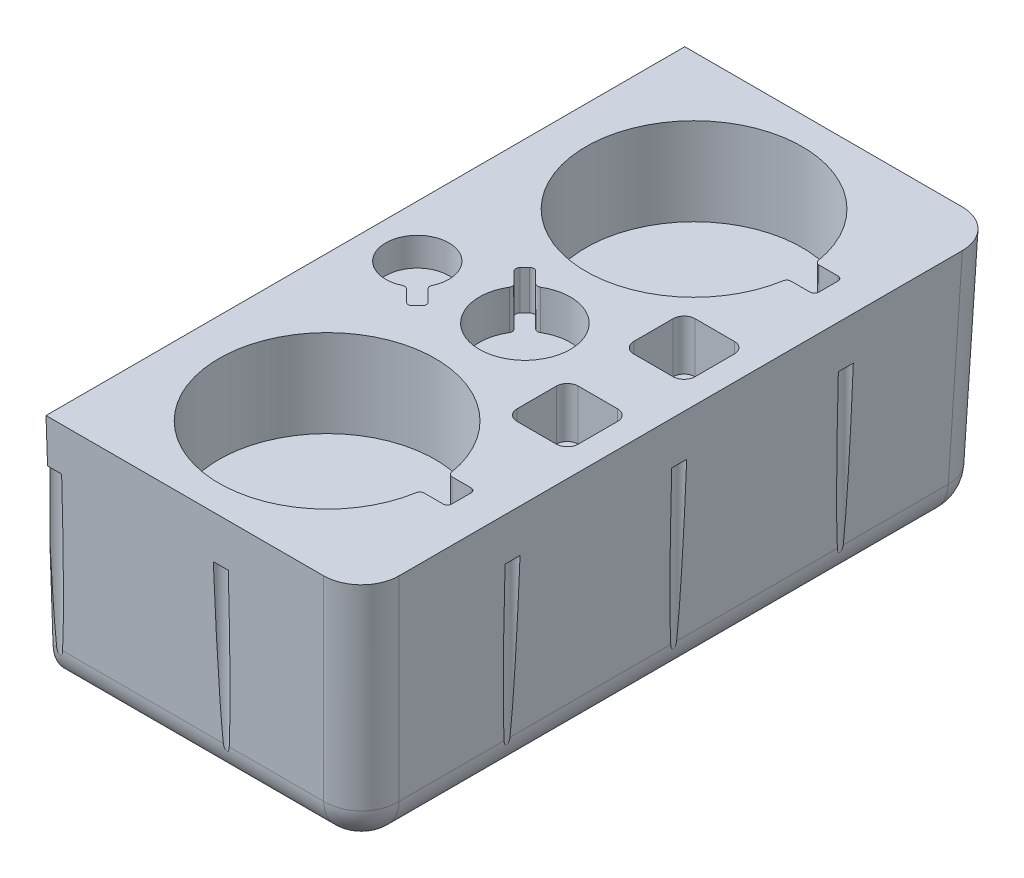
SolidWorks part; units mm, degrees
ref_plane "Front Plane" through (0, 0, 0) normal (0, 0, 1) x (1, 0, 0)
ref_plane "Top Plane" through (0, 0, 0) normal (0, 1, 0) x (1, 0, 0)
ref_plane "Right Plane" through (0, 0, 0) normal (1, 0, 0) x (0, 0, -1)
sketch "Sketch3" plane through (0, 0, 0) normal (0, 1, 0) x (1, 0, 0)
  line L1 (-70.2, -142.24) -> (70.2, -142.24)
  line L2 (-70.2, -142.24) -> (-70.2, 142.24)
  line L3 (-70.2, 142.24) -> (70.2, 142.24)
  line L4 (70.2, -142.24) -> (70.2, 142.24)
  line L5 (-70.2, -142.24) -> (70.2, 142.24) construction
  line L6 (-70.2, 142.24) -> (70.2, -142.24) construction
  point P0 (0, 0)
  dimension "D1" = 140.4
  dimension "D2" = 284.48
extrude "Boss-Extrude1" add sketch "Sketch3" along normal blind 109.22 draft 2 draft outward yes
sketch "Sketch1" plane through (0, 0, 0) normal (0, 1, 0) x (1, 0, 0)
  line L0 (45.236, 90.304) -> (57.636, 90.304)
  line L5 (57.636, 90.304) -> (57.636, 77.504)
  line L6 (57.636, 77.504) -> (45.236, 77.504)
  line L7 (45.236, -77.504) -> (57.636, -77.504)
  line L8 (57.636, -77.504) -> (57.636, -90.304)
  line L9 (57.636, -90.304) -> (45.236, -90.304)
  line L16 (39.838, 12.7) -> (57.838, 12.7)
  line L17 (34.838, 17.7) -> (34.838, 35.7)
  line L18 (39.838, 40.7) -> (57.838, 40.7)
  line L19 (62.838, 17.7) -> (62.838, 35.7)
  line L20 (34.838, 12.7) -> (62.838, 40.7) construction
  line L21 (34.838, 40.7) -> (62.838, 12.7) construction
  line L22 (39.838, -40.7) -> (57.838, -40.7)
  line L23 (34.838, -35.7) -> (34.838, -17.7)
  line L24 (39.838, -12.7) -> (57.838, -12.7)
  line L25 (62.838, -35.7) -> (62.838, -17.7)
  line L26 (34.838, -40.7) -> (62.838, -12.7) construction
  line L27 (34.838, -12.7) -> (62.838, -40.7) construction
  line L28 (-72.9829, 0) -> (78.453, 0) construction
  line L29 (74.014, 146.054) -> (-74.014, 146.054) construction
  line L31 (-74.014, 146.054) -> (-74.014, -146.054) construction
  line L34 (74.014, -146.054) -> (74.014, 146.054) construction
  line L35 (-74.014, -146.054) -> (74.014, -146.054) construction
  line L42 (-16.8542, 24.539) -> (-9.2882, 16.973)
  line L43 (-16.8542, 24.539) -> (-21.804, 19.5893)
  line L44 (-21.804, 19.5893) -> (-14.2379, 12.0232)
  line L45 (-19.3291, 22.0641) -> (2.735, 0) construction
  line L46 (-46.4604, 0) -> (-28.7687, -17.6916) construction
  line L47 (-39.0218, -12.3883) -> (-31.2436, -20.1665)
  line L48 (-31.2436, -20.1665) -> (-26.2939, -15.2167)
  line L49 (-26.2939, -15.2167) -> (-34.072, -7.4386)
  arc A0 (45.236, 90.304) -> (45.236, 77.504) centre (-3.798, 83.904) ccw
  arc A1 (45.236, -77.504) -> (45.236, -90.304) centre (-3.798, -83.904) ccw
  arc A4 (57.838, 40.7) -> (62.838, 35.7) centre (57.838, 35.7) cw
  arc A5 (57.838, 12.7) -> (62.838, 17.7) centre (57.838, 17.7) ccw
  arc A6 (39.838, 12.7) -> (34.838, 17.7) centre (39.838, 17.7) cw
  arc A7 (34.838, 35.7) -> (39.838, 40.7) centre (39.838, 35.7) cw
  arc A8 (39.838, -40.7) -> (34.838, -35.7) centre (39.838, -35.7) cw
  arc A9 (57.838, -40.7) -> (62.838, -35.7) centre (57.838, -35.7) ccw
  arc A10 (57.838, -12.7) -> (62.838, -17.7) centre (57.838, -17.7) cw
  arc A11 (34.838, -17.7) -> (39.838, -12.7) centre (39.838, -17.7) cw
  arc A12 (-34.072, -7.4386) -> (-39.0218, -12.3883) centre (-46.4604, 0) ccw
  arc A16 (-14.2379, 12.0232) -> (-9.2882, 16.973) centre (2.735, 0) ccw
  circle A17 centre (48.838, 26.7) radius 8.35
  circle A18 centre (48.838, -26.7) radius 8.35
  point P13 (48.838, 12.7)
  point P25 (48.838, 26.7)
  point P42 (48.838, -26.7)
  dimension "D3" = 98.9
  dimension "D4" = 98.9
  dimension "D8" = 20.8
  dimension "D11" = 11.303
  dimension "D15" = 5
  dimension "D18" = 5
  dimension "D5" = 12.7
  dimension "D19" = 77.8121
  dimension "D20" = 12.7
  dimension "D21" = 28.9
  dimension "D22" = 135
  dimension "D23" = 7
  dimension "D25" = 12.7
  dimension "D12" = 13.1037
  dimension "D13" = 45
  dimension "D27" = 16.7
  dimension "D1" = 12.4
  dimension "D2" = 12.8
  dimension "D6" = 12.8
  dimension "D7" = 12.4
  dimension "D9" = 7
  dimension "D10" = 10.7
  dimension "D14" = 28
  dimension "D16" = 28
  dimension "D17" = 28
  dimension "D24" = 11
  dimension "D26" = 11.176
fillet "Fillet1" radius 17.272 5 edges at (0, 0, -142.24) (0, 0, 142.24) (70.2, 0, 0) (72.107, 54.61, -144.147) (72.107, 54.61, 144.147)
extrude "Cut-Extrude1" cut sketch "Sketch1" against normal blind 40 from surface contours A0 L6 L5 L0 | A1 L9 L8 L7 starting at face at (20.1096, 109.22, 0)
extrude "Cut-Extrude2" cut sketch "Sketch1<4>" against normal blind 13 from surface contours L49 A12 L47 L48 region at (-45.034, 0, 1.4263) starting at face at (26.815, 109.22, 83.904)
sketch "Sketch1<4>" plane through (0, 0, 0) normal (0, 1, 0) x (1, 0, 0) same geometry as "Sketch1"
extrude "Cut-Extrude3" cut sketch "Sketch1<5>" against normal blind 18 from surface contours L44 A16 L42 L43 region at (1.7934, 0, -0.9416) starting at face at (-37.6906, 109.22, 8.7697)
sketch "Sketch1<5>" plane through (0, 0, 0) normal (0, 1, 0) x (1, 0, 0) same geometry as "Sketch1"
extrude "Cut-Extrude5" cut sketch "Sketch1<6>" against normal blind 23 from surface contours A7 L17 A6 L16 A5 L19 A4 L18 | A11 L23 A8 L22 A9 L25 A10 L24 region at (36.5825, 0, -14.4445) region at (36.5825, 0, 38.9555) starting at face at (-8.2446, 109.22, -10.9796)
sketch "Sketch1<6>" plane through (0, 0, 0) normal (0, 1, 0) x (1, 0, 0) same geometry as "Sketch1"
extrude "Cut-Extrude7" cut sketch "Sketch1<7>" against normal blind 31 from surface contours A17 | A18 region at (48.838, 0, -26.7) region at (48.838, 0, 26.7) starting at face at (48.838, 109.22, 26.7)
sketch "Sketch1<7>" plane through (0, 0, 0) normal (0, 1, 0) x (1, 0, 0) same geometry as "Sketch1"
fillet "Fillet2" radius 2 16 edges at (45.236, 89.22, 90.304) (45.236, 89.22, 77.504) (57.636, 89.22, 77.504) (57.636, 89.22, 90.304) (-31.2436, 102.72, 20.1665) (-26.2939, 102.72, 15.2167) (-34.072, 102.72, 7.4386) (-39.0218, 102.72, 12.3883) (-14.2379, 100.22, -12.0232) (-21.804, 100.22, -19.5893) (-16.8542, 100.22, -24.539) (-9.2882, 100.22, -16.973) (45.236, 89.22, -77.504) (57.636, 89.22, -90.304) (57.636, 89.22, -77.504) (45.236, 89.22, -90.304)
sketch "Sketch4" plane through (0, 0, 0) normal (0, 0, 1) x (1, 0, 0)
  line L1 (-74.014, 109.22) -> (56.7526, 109.22) construction
  line L2 (-70.2, 109.22) -> (-70.2, 0)
  line L3 (-70.2, 0) -> (-85.4637, 109.22)
  line L4 (-85.4637, 109.22) -> (-70.2, 109.22)
  dimension "D2" = 110.2814
extrude "Cut-Extrude8" cut sketch "Sketch4" against normal through all both and the other way through all contours L3 L4 L2
ref_plane "Plane1" through (0, 88.9, 0) normal (0, 1, 0) x (1, 0, 0)
sketch "Sketch6" plane through (0, 88.9, 0) normal (0, 1, 0) x (1, 0, 0)
  line L0 (74.014, -128.7926) -> (74.014, 128.7926) construction
  line L1 (74.014, 3.5) -> (74.014, -3.5)
  line L2 (74.014, 79.7) -> (74.014, 72.7)
  line L3 (-9.7237, 0) -> (10.798, 0) construction
  line L4 (74.014, -79.7) -> (74.014, -72.7)
  line L5 (56.7526, 146.054) -> (-70.2, 146.054) construction
  line L6 (5.514, 146.054) -> (12.514, 146.054)
  line L7 (-70.686, 146.054) -> (-63.686, 146.054)
  line L8 (-70.686, -146.054) -> (-63.686, -146.054)
  line L9 (5.514, -146.054) -> (12.514, -146.054)
  arc A0 (74.014, 3.5) -> (74.014, -3.5) centre (74.014, 0) ccw
  arc A1 (74.014, 79.7) -> (74.014, 72.7) centre (74.014, 76.2) ccw
  arc A2 (74.014, -79.7) -> (74.014, -72.7) centre (74.014, -76.2) cw
  arc A3 (5.514, 146.054) -> (12.514, 146.054) centre (9.014, 146.054) ccw
  arc A4 (-70.686, 146.054) -> (-63.686, 146.054) centre (-67.186, 146.054) ccw
  arc A5 (-70.686, -146.054) -> (-63.686, -146.054) centre (-67.186, -146.054) cw
  arc A6 (5.514, -146.054) -> (12.514, -146.054) centre (9.014, -146.054) cw
  dimension "D1" = 7
  dimension "D2" = 76.2
  dimension "D3" = 65
  dimension "D4" = 76.2
extrude "Cut-Extrude9" cut sketch "Sketch6" against normal up to next
